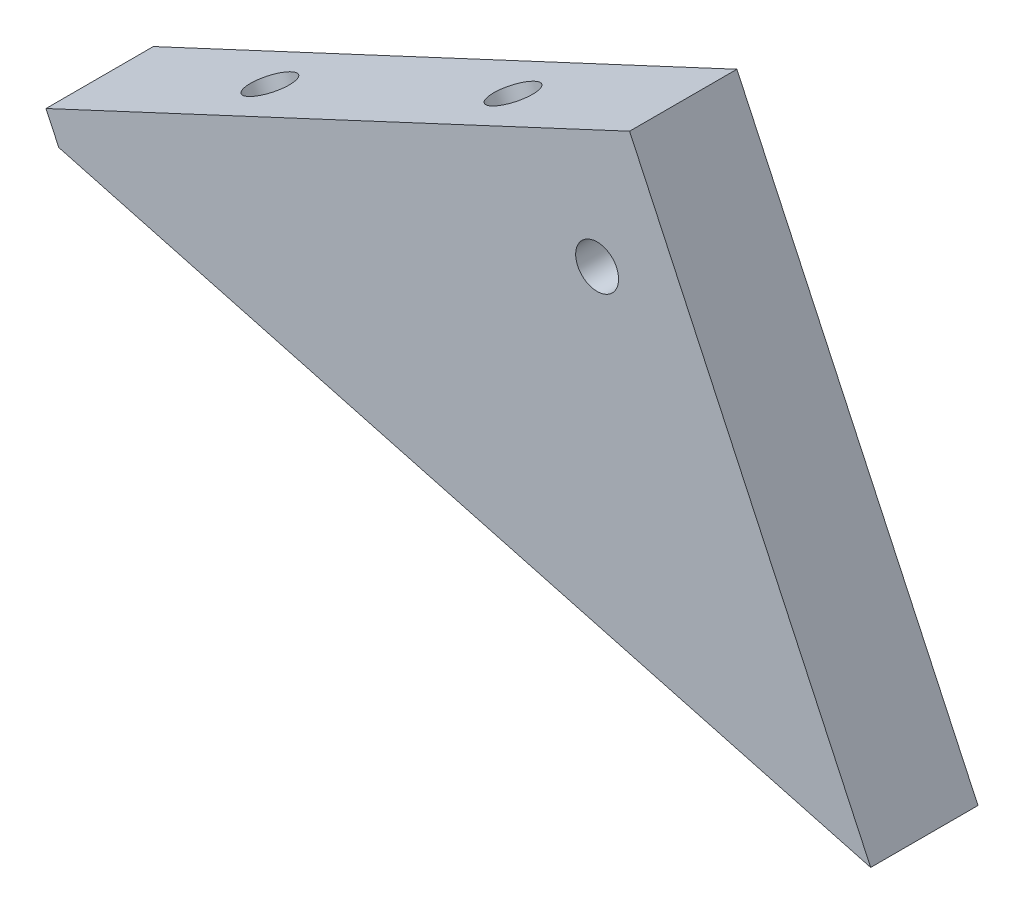
SolidWorks part; units mm, degrees
material "ABS"
ref_plane "Front Plane" through (0, 0, 0) normal (0, 0, 1) x (1, 0, 0)
ref_plane "Top Plane" through (0, 0, 0) normal (0, 1, 0) x (1, 0, 0)
ref_plane "Right Plane" through (0, 0, 0) normal (1, 0, 0) x (0, 0, -1)
sketch "Sketch1" plane through (0, 0, 0) normal (0, 0, 1) x (1, 0, 0)
  line L0 (130.6366, -19.5934) -> (108.169, 28.5884)
  line L1 (-85.1981, -61.5801) -> (277.3251, 107.4672) construction
  line L2 (108.169, 28.5884) -> (53.7905, 3.2313)
  line L3 (53.7905, 3.2313) -> (54.981, 0.6784)
  line L4 (54.981, 0.6784) -> (130.6366, -19.5934)
  line L5 (130.6366, -19.5934) -> (108.169, 28.5884) construction
  line L7 (50.7481, 1.8126) -> (264.8848, -55.5651) construction
  dimension "D1" = 60
extrude "Boss-Extrude1" add sketch "Sketch1" against normal blind 10
sketch "Sketch2" plane through (8.3697, -17.9488, 0) normal (-0.4226, 0.9063, 0) x (0.9063, 0.4226, 0)
  line L0 (50.1164, 5) -> (110.1164, 5) construction
  line L1 (50.1164, 10) -> (50.1164, 0) construction
  line L2 (110.1164, 10) -> (110.1164, 0) construction
  line L3 (80.1164, 10) -> (80.1164, 0) construction
  line L4 (92.6164, 0.9585) -> (96.1164, 2.9793)
  line L5 (96.1164, 2.9793) -> (96.1164, 7.0207)
  line L6 (96.1164, 7.0207) -> (92.6164, 9.0415)
  line L7 (92.6164, 9.0415) -> (89.1164, 7.0207)
  line L8 (89.1164, 7.0207) -> (89.1164, 2.9793)
  line L9 (89.1164, 2.9793) -> (92.6164, 0.9585)
  line L10 (110.1164, 10) -> (50.1164, 10) construction
  line L11 (110.1164, 0) -> (50.1164, 0) construction
  line L12 (71.1164, 2.9793) -> (67.6164, 0.9585)
  line L13 (67.6164, 0.9585) -> (64.1164, 2.9793)
  line L14 (71.1164, 7.0207) -> (71.1164, 2.9793)
  line L15 (67.6164, 9.0415) -> (71.1164, 7.0207)
  line L16 (64.1164, 7.0207) -> (67.6164, 9.0415)
  line L17 (64.1164, 2.9793) -> (64.1164, 7.0207)
  circle A0 centre (92.6164, 5) radius 3.5 construction
  circle A1 centre (92.6164, 5) radius 2
  circle A2 centre (67.6164, 5) radius 3.5 construction
  circle A3 centre (67.6164, 5) radius 2
  dimension "D3" = 4
  dimension "D1" = 17.5
  dimension "D2" = 7
extrude "Cut-Extrude1" cut sketch "Sketch2" against normal through all contours A3 | A1 region at (92.3086, 21.1926, -5) region at (69.6509, 10.6271, -5)
extrude "Cut-Extrude2" cut sketch "Sketch2<3>" against normal through all from offset 4 offset against normal yes
sketch "Sketch2<3>" plane through (8.3697, -17.9488, 0) normal (-0.4226, 0.9063, 0) x (0.9063, 0.4226, 0) same geometry as "Sketch2"
sketch "Sketch3" plane through (3.8526, 14.3782, 0) normal (-0.2588, -0.9659, 0) x (0.9659, -0.2588, 0)
  line L0 (131.2564, -5) -> (52.9319, -5) construction
  line L1 (131.2564, -10) -> (131.2564, 0) construction
  line L2 (52.9319, -10) -> (52.9319, 0) construction
  circle A0 centre (86.1987, -5) radius 2
  circle A1 centre (111.8, -5) radius 2
  circle A2 centre (111.8, -5) radius 1.5 construction
  circle A3 centre (86.1987, -5) radius 1.5 construction
  dimension "D1" = 4
  dimension "D2" = 4
extrude "Cut-Extrude3" cut sketch "Sketch3" against normal blind 10
sketch "Sketch4" plane through (0, 0, 0) normal (0, 0, 1) x (1, 0, 0)
  line L0 (130.6366, -19.5934) -> (108.169, 28.5884) construction
  line L1 (109.1708, 15.7922) -> (107.4628, 19.455)
  line L2 (107.4628, 19.455) -> (103.4367, 19.8072)
  line L3 (103.4367, 19.8072) -> (101.1187, 16.4966)
  line L4 (101.1187, 16.4966) -> (102.8266, 12.8338)
  line L5 (102.8266, 12.8338) -> (106.8527, 12.4816)
  line L6 (106.8527, 12.4816) -> (109.1708, 15.7922)
  line L7 (108.169, 28.5884) -> (53.7905, 3.2313) construction
  circle A0 centre (105.1447, 16.1444) radius 2
  circle A1 centre (105.1447, 16.1444) radius 3.5 construction
  dimension "D4" = 4
  dimension "D1" = 8
  dimension "D2" = 10
  dimension "D3" = 7
  dimension "D5" = 0
extrude "Cut-Extrude4" cut sketch "Sketch4" against normal blind 10 contours A0 region at (105.1447, 16.1444, 0)
extrude "Cut-Extrude5" cut sketch "Sketch4<3>" along normal blind 5 from surface starting at face at (107.1447, 16.1444, -10)
sketch "Sketch4<3>" plane through (0, 0, 0) normal (0, 0, 1) x (1, 0, 0) same geometry as "Sketch4"
